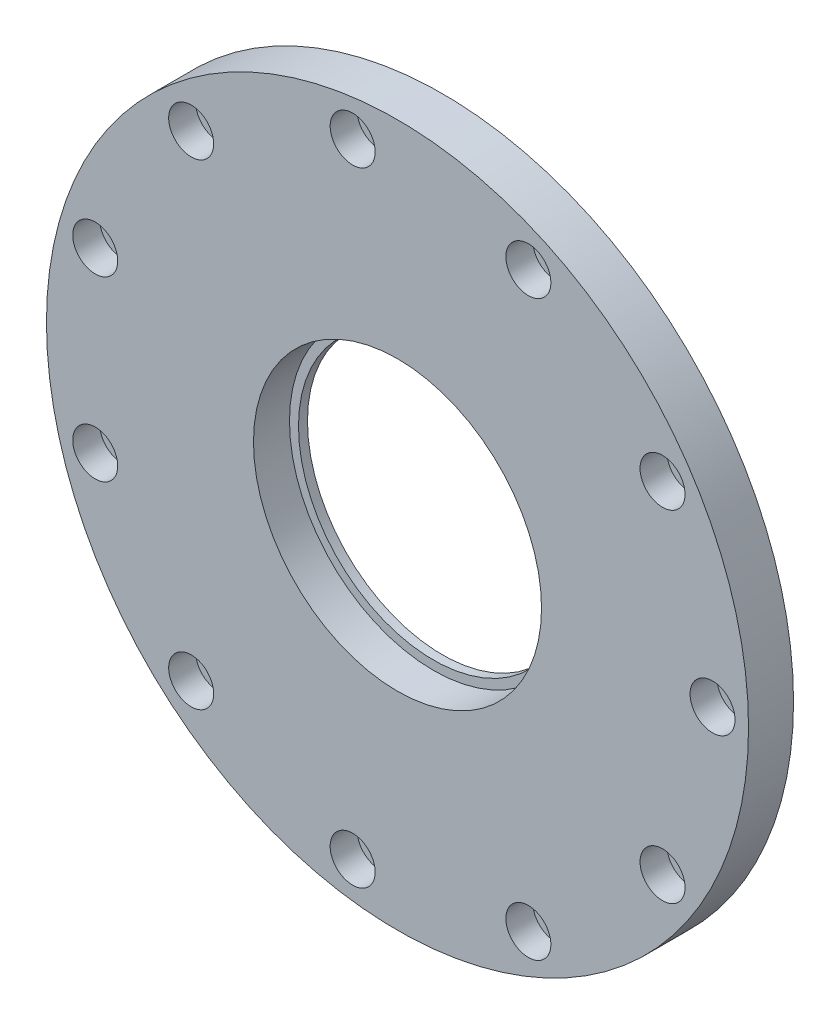
SolidWorks part; units mm, degrees
ref_plane "Front Plane" through (0, 0, 0) normal (0, 0, 1) x (1, 0, 0)
ref_plane "Top Plane" through (0, 0, 0) normal (0, 1, 0) x (1, 0, 0)
ref_plane "Right Plane" through (0, 0, 0) normal (1, 0, 0) x (0, 0, -1)
sketch "Sketch1" plane through (0, 0, 0) normal (0, 0, 1) x (1, 0, 0)
  circle A0 centre (0, 0) radius 39
  circle A1 centre (0, 0) radius 35 construction
  circle A2 centre (35, 0) radius 2.5
  circle A3 centre (29.4439, -18.9224) radius 2.5
  circle A4 centre (14.5395, -31.8371) radius 2.5
  circle A5 centre (-4.981, -34.6438) radius 2.5
  circle A6 centre (-22.9201, -26.4512) radius 2.5
  circle A7 centre (-33.5823, -9.8606) radius 2.5
  circle A8 centre (-33.5823, 9.8606) radius 2.5
  circle A9 centre (-22.9201, 26.4512) radius 2.5
  circle A10 centre (-4.981, 34.6438) radius 2.5
  circle A11 centre (14.5395, 31.8371) radius 2.5
  circle A12 centre (29.4439, 18.9224) radius 2.5
  circle A13 centre (0, 0) radius 16
  point P28 (0, 0)
extrude "Boss-Extrude1" add sketch "Sketch1" along normal blind 3
sketch "Sketch2" plane through (0, 0, 0) normal (0, 0, -1) x (-1, 0, 0)
  circle A0 centre (0, 0) radius 16
  circle A1 centre (0, 0) radius 39
  dimension "D1" = 32
extrude "Boss-Extrude2" add sketch "Sketch2" along normal blind 2 contours A1 | A0
sketch "Sketch3" plane through (0, 0, 3) normal (0, 0, 1) x (1, 0, 0)
  circle A0 centre (35, 0) radius 1.6
  circle A1 centre (29.4439, -18.9224) radius 1.6
  circle A2 centre (14.5395, -31.8371) radius 1.6
  circle A3 centre (-4.981, -34.6438) radius 1.6
  circle A4 centre (-22.9201, -26.4512) radius 1.6
  circle A5 centre (-33.5823, -9.8606) radius 1.6
  circle A6 centre (-33.5823, 9.8606) radius 1.6
  circle A7 centre (-22.9201, 26.4512) radius 1.6
  circle A8 centre (-4.981, 34.6438) radius 1.6
  circle A9 centre (14.5395, 31.8371) radius 1.6
  circle A10 centre (29.4439, 18.9224) radius 1.6
  point P3 (0, 0)
  point P25 (0, 0)
  dimension "D1" = 3.2
  dimension "D2" = 11
extrude "Cut-Extrude1" cut sketch "Sketch3" against normal through all
sketch "Sketch4" plane through (0, 0, -2) normal (0, 0, -1) x (-1, 0, 0)
  circle A0 centre (0, 0) radius 16
  circle A1 centre (0, 0) radius 15
  dimension "D1" = 32
  dimension "D2" = 30
extrude "Boss-Extrude3" add sketch "Sketch4" against normal blind 1
